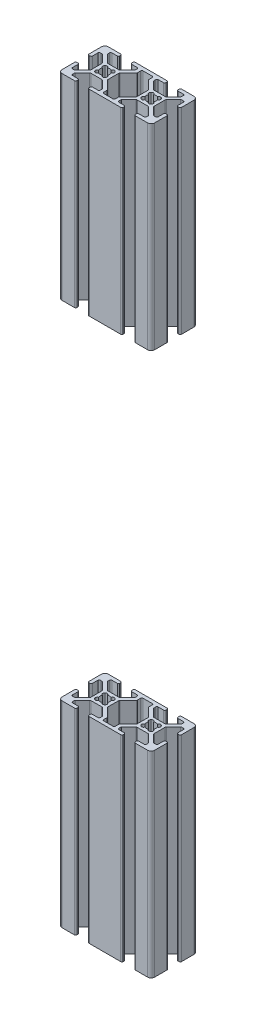
SolidWorks part; units mm, degrees
ref_plane "前视基准面" through (0, 0, 0) normal (0, 0, 1) x (1, 0, 0)
ref_plane "上视基准面" through (0, 0, 0) normal (0, 1, 0) x (1, 0, 0)
ref_plane "右视基准面" through (0, 0, 0) normal (1, 0, 0) x (0, 0, -1)
other "Configuration Table"
sketch "草图1" plane through (0, 0, 0) normal (0, 1, 0) x (1, 0, 0)
  line L0 (17.2471, 7.2074) -> (17.0675, 7.387)
  line L5 (17.0675, 11.6368) -> (17.2471, 11.8164)
  line L6 (21.4969, 11.8164) -> (21.6765, 11.6368)
  line L7 (21.6765, 7.387) -> (21.4969, 7.2074)
  line L8 (6.867, 1.5199) -> (6.867, 2.8671)
  line L9 (6.7182, 3.2263) -> (3.1758, 6.7687)
  line L10 (3.027, 7.128) -> (3.027, 11.8958)
  line L11 (3.1758, 12.255) -> (6.7182, 15.7974)
  line L26 (6.867, 16.1566) -> (6.867, 17.5039)
  line L41 (7.375, 18.0119) -> (11.369, 18.0119)
  line L56 (11.877, 17.5039) -> (11.877, 16.1566)
  line L71 (12.0258, 15.7974) -> (15.5682, 12.255)
  line L72 (15.717, 11.8958) -> (15.717, 7.128)
  line L73 (15.5682, 6.7687) -> (12.0258, 3.2263)
  line L74 (11.877, 2.8671) -> (11.877, 1.5199)
  line L75 (11.369, 1.0119) -> (7.375, 1.0119)
  line L76 (-2.7529, 7.2074) -> (-2.9325, 7.387)
  line L77 (-2.9325, 11.6368) -> (-2.7529, 11.8164)
  line L78 (1.4969, 11.8164) -> (1.6765, 11.6368)
  line L79 (1.6765, 7.387) -> (1.4969, 7.2074)
  line L80 (-3.0119, 5.8569) -> (1.7559, 5.8569)
  line L81 (2.1151, 5.7081) -> (5.2182, 2.605)
  line L82 (5.367, 2.2458) -> (5.367, 1.5199)
  line L83 (4.859, 1.0119) -> (2.51, 1.0119)
  line L84 (2.002, 0.5039) -> (2.002, 0.0199)
  line L85 (2.51, -0.4881) -> (16.234, -0.4881)
  line L86 (16.742, 0.0199) -> (16.742, 0.5039)
  line L87 (16.234, 1.0119) -> (13.885, 1.0119)
  line L88 (13.377, 1.5199) -> (13.377, 2.2458)
  line L89 (13.5258, 2.605) -> (16.6289, 5.7081)
  line L90 (16.9881, 5.8569) -> (21.7559, 5.8569)
  line L91 (22.1151, 5.7081) -> (25.2182, 2.605)
  line L92 (25.367, 2.2458) -> (25.367, 1.5199)
  line L93 (24.859, 1.0119) -> (22.51, 1.0119)
  line L94 (22.002, 0.5039) -> (22.002, 0.0199)
  line L95 (22.51, -0.4881) -> (27.872, -0.4881)
  line L96 (29.372, 1.0119) -> (29.372, 6.3739)
  line L97 (28.864, 6.8819) -> (28.38, 6.8819)
  line L98 (27.872, 6.3739) -> (27.872, 4.0249)
  line L99 (27.364, 3.5169) -> (26.6381, 3.5169)
  line L100 (26.2789, 3.6657) -> (23.1758, 6.7687)
  line L101 (23.027, 7.128) -> (23.027, 11.8958)
  line L102 (23.1758, 12.255) -> (26.2789, 15.3581)
  line L103 (26.6381, 15.5069) -> (27.364, 15.5069)
  line L104 (27.872, 14.9989) -> (27.872, 12.6499)
  line L105 (28.38, 12.1419) -> (28.864, 12.1419)
  line L106 (29.372, 12.6499) -> (29.372, 18.0119)
  line L107 (27.872, 19.5119) -> (22.51, 19.5119)
  line L108 (22.002, 19.0039) -> (22.002, 18.5199)
  line L109 (22.51, 18.0119) -> (24.859, 18.0119)
  line L110 (25.367, 17.5039) -> (25.367, 16.778)
  line L111 (25.2182, 16.4187) -> (22.1151, 13.3157)
  line L112 (21.7559, 13.1669) -> (16.9881, 13.1669)
  line L113 (16.6289, 13.3157) -> (13.5258, 16.4187)
  line L114 (13.377, 16.778) -> (13.377, 17.5039)
  line L115 (13.885, 18.0119) -> (16.234, 18.0119)
  line L116 (16.742, 18.5199) -> (16.742, 19.0039)
  line L117 (16.234, 19.5119) -> (2.51, 19.5119)
  line L118 (2.002, 19.0039) -> (2.002, 18.5199)
  line L119 (2.51, 18.0119) -> (4.859, 18.0119)
  line L120 (5.367, 17.5039) -> (5.367, 16.778)
  line L121 (5.2182, 16.4187) -> (2.1151, 13.3157)
  line L122 (1.7559, 13.1669) -> (-3.0119, 13.1669)
  line L123 (-3.3711, 13.3157) -> (-6.4742, 16.4187)
  line L124 (-6.623, 16.778) -> (-6.623, 17.5039)
  line L125 (-6.115, 18.0119) -> (-3.766, 18.0119)
  line L126 (-3.258, 18.5199) -> (-3.258, 19.0039)
  line L127 (-3.766, 19.5119) -> (-9.128, 19.5119)
  line L128 (-10.628, 18.0119) -> (-10.628, 12.6499)
  line L129 (-10.12, 12.1419) -> (-9.636, 12.1419)
  line L130 (-9.128, 12.6499) -> (-9.128, 14.9989)
  line L131 (-8.62, 15.5069) -> (-7.8941, 15.5069)
  line L132 (-7.5349, 15.3581) -> (-4.4318, 12.255)
  line L133 (-4.283, 11.8958) -> (-4.283, 7.128)
  line L134 (-4.4318, 6.7687) -> (-7.5349, 3.6657)
  line L135 (-7.8941, 3.5169) -> (-8.62, 3.5169)
  line L136 (-9.128, 4.0249) -> (-9.128, 6.3739)
  line L137 (-9.636, 6.8819) -> (-10.12, 6.8819)
  line L138 (-10.628, 6.3739) -> (-10.628, 1.0119)
  line L139 (-9.128, -0.4881) -> (-3.766, -0.4881)
  line L140 (-3.258, 0.0199) -> (-3.258, 0.5039)
  line L141 (-3.766, 1.0119) -> (-6.115, 1.0119)
  line L142 (-6.623, 1.5199) -> (-6.623, 2.2458)
  line L143 (-6.4742, 2.605) -> (-3.3711, 5.7081)
  arc A5 (17.4369, 8.7079) -> (17.0675, 7.387) centre (17.624, 7.9435) ccw
  arc A6 (17.4369, 10.3158) -> (17.4369, 8.7079) centre (19.372, 9.5119) ccw
  arc A7 (17.0675, 11.6368) -> (17.4369, 10.3158) centre (17.624, 11.0803) ccw
  arc A8 (18.568, 11.447) -> (17.2471, 11.8164) centre (17.8036, 11.2599) ccw
  arc A9 (20.176, 11.447) -> (18.568, 11.447) centre (19.372, 9.5119) ccw
  arc A10 (21.4969, 11.8164) -> (20.176, 11.447) centre (20.9404, 11.2599) ccw
  arc A11 (21.3071, 10.3158) -> (21.6765, 11.6368) centre (21.12, 11.0803) ccw
  arc A12 (21.3071, 8.7079) -> (21.3071, 10.3158) centre (19.372, 9.5119) ccw
  arc A13 (21.6765, 7.387) -> (21.3071, 8.7079) centre (21.12, 7.9435) ccw
  arc A14 (20.176, 7.5767) -> (21.4969, 7.2074) centre (20.9404, 7.7639) ccw
  arc A15 (18.568, 7.5767) -> (20.176, 7.5767) centre (19.372, 9.5119) ccw
  arc A16 (17.2471, 7.2074) -> (18.568, 7.5767) centre (17.8036, 7.7639) ccw
  arc A17 (6.867, 1.5199) -> (7.375, 1.0119) centre (7.375, 1.5199) ccw
  arc A18 (6.867, 2.8671) -> (6.7182, 3.2263) centre (6.359, 2.8671) ccw
  arc A19 (3.027, 7.128) -> (3.1758, 6.7687) centre (3.535, 7.128) ccw
  arc A20 (3.1758, 12.255) -> (3.027, 11.8958) centre (3.535, 11.8958) ccw
  arc A21 (6.7182, 15.7974) -> (6.867, 16.1566) centre (6.359, 16.1566) ccw
  arc A22 (7.375, 18.0119) -> (6.867, 17.5039) centre (7.375, 17.5039) ccw
  arc A23 (11.877, 17.5039) -> (11.369, 18.0119) centre (11.369, 17.5039) ccw
  arc A24 (11.877, 16.1566) -> (12.0258, 15.7974) centre (12.385, 16.1566) ccw
  arc A25 (15.717, 11.8958) -> (15.5682, 12.255) centre (15.209, 11.8958) ccw
  arc A26 (15.5682, 6.7687) -> (15.717, 7.128) centre (15.209, 7.128) ccw
  arc A27 (12.0258, 3.2263) -> (11.877, 2.8671) centre (12.385, 2.8671) ccw
  arc A28 (11.369, 1.0119) -> (11.877, 1.5199) centre (11.369, 1.5199) ccw
  arc A29 (-2.5631, 8.7079) -> (-2.9325, 7.387) centre (-2.376, 7.9435) ccw
  arc A30 (-2.5631, 10.3158) -> (-2.5631, 8.7079) centre (-0.628, 9.5119) ccw
  arc A31 (-2.9325, 11.6368) -> (-2.5631, 10.3158) centre (-2.376, 11.0803) ccw
  arc A32 (-1.432, 11.447) -> (-2.7529, 11.8164) centre (-2.1964, 11.2599) ccw
  arc A33 (0.176, 11.447) -> (-1.432, 11.447) centre (-0.628, 9.5119) ccw
  arc A34 (1.4969, 11.8164) -> (0.176, 11.447) centre (0.9404, 11.2599) ccw
  arc A35 (1.3071, 10.3158) -> (1.6765, 11.6368) centre (1.12, 11.0803) ccw
  arc A36 (1.3071, 8.7079) -> (1.3071, 10.3158) centre (-0.628, 9.5119) ccw
  arc A37 (1.6765, 7.387) -> (1.3071, 8.7079) centre (1.12, 7.9435) ccw
  arc A38 (0.176, 7.5767) -> (1.4969, 7.2074) centre (0.9404, 7.7639) ccw
  arc A39 (-1.432, 7.5767) -> (0.176, 7.5767) centre (-0.628, 9.5119) ccw
  arc A40 (-2.7529, 7.2074) -> (-1.432, 7.5767) centre (-2.1964, 7.7639) ccw
  arc A41 (-3.0119, 5.8569) -> (-3.3711, 5.7081) centre (-3.0119, 5.3489) ccw
  arc A42 (2.1151, 5.7081) -> (1.7559, 5.8569) centre (1.7559, 5.3489) ccw
  arc A43 (5.367, 2.2458) -> (5.2182, 2.605) centre (4.859, 2.2458) ccw
  arc A44 (4.859, 1.0119) -> (5.367, 1.5199) centre (4.859, 1.5199) ccw
  arc A45 (2.51, 1.0119) -> (2.002, 0.5039) centre (2.51, 0.5039) ccw
  arc A46 (2.002, 0.0199) -> (2.51, -0.4881) centre (2.51, 0.0199) ccw
  arc A47 (16.234, -0.4881) -> (16.742, 0.0199) centre (16.234, 0.0199) ccw
  arc A48 (16.742, 0.5039) -> (16.234, 1.0119) centre (16.234, 0.5039) ccw
  arc A49 (13.377, 1.5199) -> (13.885, 1.0119) centre (13.885, 1.5199) ccw
  arc A50 (13.5258, 2.605) -> (13.377, 2.2458) centre (13.885, 2.2458) ccw
  arc A51 (16.9881, 5.8569) -> (16.6289, 5.7081) centre (16.9881, 5.3489) ccw
  arc A52 (22.1151, 5.7081) -> (21.7559, 5.8569) centre (21.7559, 5.3489) ccw
  arc A53 (25.367, 2.2458) -> (25.2182, 2.605) centre (24.859, 2.2458) ccw
  arc A54 (24.859, 1.0119) -> (25.367, 1.5199) centre (24.859, 1.5199) ccw
  arc A55 (22.51, 1.0119) -> (22.002, 0.5039) centre (22.51, 0.5039) ccw
  arc A56 (22.002, 0.0199) -> (22.51, -0.4881) centre (22.51, 0.0199) ccw
  arc A57 (27.872, -0.4881) -> (29.372, 1.0119) centre (27.872, 1.0119) ccw
  arc A58 (29.372, 6.3739) -> (28.864, 6.8819) centre (28.864, 6.3739) ccw
  arc A59 (28.38, 6.8819) -> (27.872, 6.3739) centre (28.38, 6.3739) ccw
  arc A60 (27.364, 3.5169) -> (27.872, 4.0249) centre (27.364, 4.0249) ccw
  arc A61 (26.2789, 3.6657) -> (26.6381, 3.5169) centre (26.6381, 4.0249) ccw
  arc A62 (23.027, 7.128) -> (23.1758, 6.7687) centre (23.535, 7.128) ccw
  arc A63 (23.1758, 12.255) -> (23.027, 11.8958) centre (23.535, 11.8958) ccw
  arc A64 (26.6381, 15.5069) -> (26.2789, 15.3581) centre (26.6381, 14.9989) ccw
  arc A65 (27.872, 14.9989) -> (27.364, 15.5069) centre (27.364, 14.9989) ccw
  arc A66 (27.872, 12.6499) -> (28.38, 12.1419) centre (28.38, 12.6499) ccw
  arc A67 (28.864, 12.1419) -> (29.372, 12.6499) centre (28.864, 12.6499) ccw
  arc A68 (29.372, 18.0119) -> (27.872, 19.5119) centre (27.872, 18.0119) ccw
  arc A69 (22.51, 19.5119) -> (22.002, 19.0039) centre (22.51, 19.0039) ccw
  arc A70 (22.002, 18.5199) -> (22.51, 18.0119) centre (22.51, 18.5199) ccw
  arc A71 (25.367, 17.5039) -> (24.859, 18.0119) centre (24.859, 17.5039) ccw
  arc A72 (25.2182, 16.4187) -> (25.367, 16.778) centre (24.859, 16.778) ccw
  arc A73 (21.7559, 13.1669) -> (22.1151, 13.3157) centre (21.7559, 13.6749) ccw
  arc A74 (16.6289, 13.3157) -> (16.9881, 13.1669) centre (16.9881, 13.6749) ccw
  arc A75 (13.377, 16.778) -> (13.5258, 16.4187) centre (13.885, 16.778) ccw
  arc A76 (13.885, 18.0119) -> (13.377, 17.5039) centre (13.885, 17.5039) ccw
  arc A77 (16.234, 18.0119) -> (16.742, 18.5199) centre (16.234, 18.5199) ccw
  arc A78 (16.742, 19.0039) -> (16.234, 19.5119) centre (16.234, 19.0039) ccw
  arc A79 (2.51, 19.5119) -> (2.002, 19.0039) centre (2.51, 19.0039) ccw
  arc A80 (2.002, 18.5199) -> (2.51, 18.0119) centre (2.51, 18.5199) ccw
  arc A81 (5.367, 17.5039) -> (4.859, 18.0119) centre (4.859, 17.5039) ccw
  arc A82 (5.2182, 16.4187) -> (5.367, 16.778) centre (4.859, 16.778) ccw
  arc A83 (1.7559, 13.1669) -> (2.1151, 13.3157) centre (1.7559, 13.6749) ccw
  arc A84 (-3.3711, 13.3157) -> (-3.0119, 13.1669) centre (-3.0119, 13.6749) ccw
  arc A85 (-6.623, 16.778) -> (-6.4742, 16.4187) centre (-6.115, 16.778) ccw
  arc A86 (-6.115, 18.0119) -> (-6.623, 17.5039) centre (-6.115, 17.5039) ccw
  arc A87 (-3.766, 18.0119) -> (-3.258, 18.5199) centre (-3.766, 18.5199) ccw
  arc A88 (-3.258, 19.0039) -> (-3.766, 19.5119) centre (-3.766, 19.0039) ccw
  arc A89 (-9.128, 19.5119) -> (-10.628, 18.0119) centre (-9.128, 18.0119) ccw
  arc A90 (-10.628, 12.6499) -> (-10.12, 12.1419) centre (-10.12, 12.6499) ccw
  arc A91 (-9.636, 12.1419) -> (-9.128, 12.6499) centre (-9.636, 12.6499) ccw
  arc A92 (-8.62, 15.5069) -> (-9.128, 14.9989) centre (-8.62, 14.9989) ccw
  arc A93 (-7.5349, 15.3581) -> (-7.8941, 15.5069) centre (-7.8941, 14.9989) ccw
  arc A94 (-4.283, 11.8958) -> (-4.4318, 12.255) centre (-4.791, 11.8958) ccw
  arc A95 (-4.4318, 6.7687) -> (-4.283, 7.128) centre (-4.791, 7.128) ccw
  arc A96 (-7.8941, 3.5169) -> (-7.5349, 3.6657) centre (-7.8941, 4.0249) ccw
  arc A97 (-9.128, 4.0249) -> (-8.62, 3.5169) centre (-8.62, 4.0249) ccw
  arc A98 (-9.128, 6.3739) -> (-9.636, 6.8819) centre (-9.636, 6.3739) ccw
  arc A99 (-10.12, 6.8819) -> (-10.628, 6.3739) centre (-10.12, 6.3739) ccw
  arc A100 (-10.628, 1.0119) -> (-9.128, -0.4881) centre (-9.128, 1.0119) ccw
  arc A101 (-3.766, -0.4881) -> (-3.258, 0.0199) centre (-3.766, 0.0199) ccw
  arc A102 (-3.258, 0.5039) -> (-3.766, 1.0119) centre (-3.766, 0.5039) ccw
  arc A103 (-6.623, 1.5199) -> (-6.115, 1.0119) centre (-6.115, 1.5199) ccw
  arc A104 (-6.4742, 2.605) -> (-6.623, 2.2458) centre (-6.115, 2.2458) ccw
extrude "凸台-拉伸1" add sketch "草图1" along normal mid plane 320
sketch "草图2" plane through (0, 0, -19.5119) normal (0, 0, -1) x (-1, 0, 0)
  line L0 (-29.372, 160) -> (-29.372, -160) construction
  line L1 (-29.372, 75) -> (10.628, 75)
  line L2 (-29.372, 75) -> (-29.372, -75)
  line L3 (-29.372, -75) -> (10.628, -75)
  line L4 (10.628, 75) -> (10.628, -75)
  line L5 (10.628, 160) -> (10.628, -160) construction
  line L6 (-16.234, 160) -> (-2.51, 160) construction
  line L7 (-16.234, -160) -> (-2.51, -160) construction
  dimension "D1" = 40
  dimension "D2" = 85
  dimension "D3" = 85
extrude "切除-拉伸1" cut sketch "草图2" against normal blind 32
